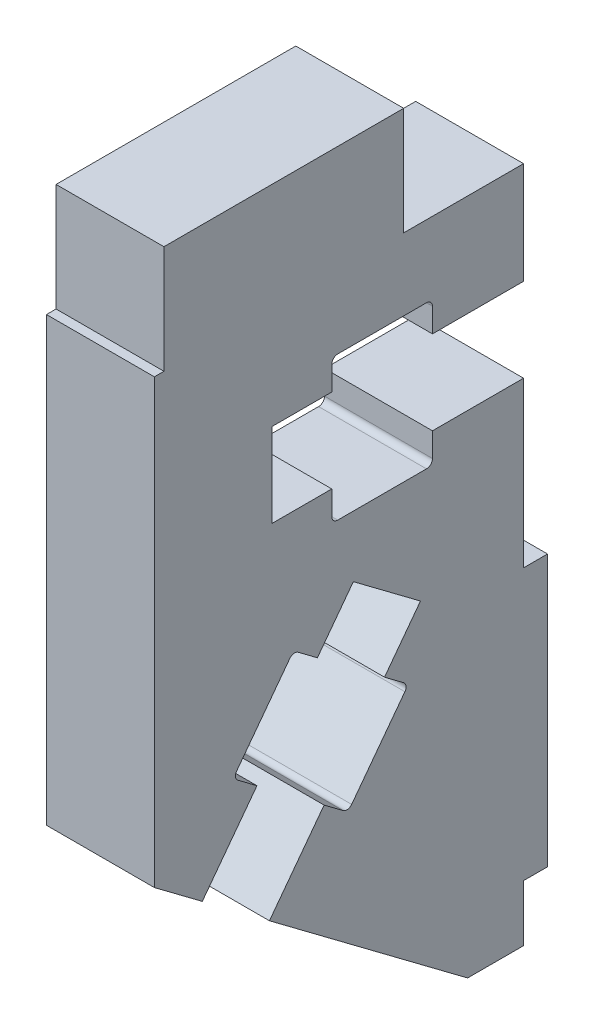
SolidWorks part; units mm, degrees
ref_plane "Front Plane" through (0, 0, 0) normal (0, 0, 1) x (1, 0, 0)
ref_plane "Top Plane" through (0, 0, 0) normal (0, 1, 0) x (1, 0, 0)
ref_plane "Right Plane" through (0, 0, 0) normal (1, 0, 0) x (0, 0, -1)
sketch "Sketch1" plane through (0, 0, 0) normal (1, 0, 0) x (0, 0, -1)
  line L0 (0, 0) -> (0, -30)
  line L1 (0, -30) -> (-40, 0)
  line L2 (-40, 0) -> (0, 0)
  dimension "D1" = 40
  dimension "D2" = 30
extrude "Boss-Extrude1" add sketch "Sketch1" along normal blind 4.5
sketch "Sketch2" plane through (4.5, 0, 0) normal (1, 0, 0) x (0, 0, -1)
  line L0 (0, -25.9) -> (1, -25.9)
  line L1 (0, -30) -> (0, 0) construction
  line L2 (1, -25.9) -> (1, -14.6)
  line L3 (1, -14.6) -> (0, -14.6)
  line L4 (0, -14.6) -> (0, -25.9)
  line L5 (1, -20.25) -> (0, -20.25) construction
  line L6 (0, -14.5) -> (4.5, -14.5) construction
  line L7 (0, -26) -> (4.5, -26) construction
  dimension "D2" = 1
  dimension "D3" = 0.1
  dimension "D1" = 0.1
extrude "Boss-Extrude2" add sketch "Sketch2" against normal through all
sketch "Sketch3" plane through (4.5, 0, 0) normal (1, 0, 0) x (0, 0, -1)
  line L0 (0, -6) -> (-10.5, -6) construction
  line L1 (0, -14.6) -> (0, 0) construction
  line L2 (-10.5, -7.75) -> (-10.5, -4.25) construction
  line L3 (-10.5, -4.25) -> (0, -4.25) construction
  line L4 (0, -4.25) -> (-3.8, -4.25)
  line L5 (-3.8, -4.25) -> (-3.8, -3.25)
  line L6 (-4.05, -3) -> (-7.75, -3)
  line L7 (-8, -3.25) -> (-8, -4.25)
  line L8 (-8, -4.25) -> (-10.5, -4.25)
  line L9 (-10.5, -4.25) -> (-10.5, -7.75)
  line L10 (0, -4.25) -> (0, -7.75)
  line L12 (-10.5, -7.75) -> (0, -7.75) construction
  line L13 (-8, -7.75) -> (-10.5, -7.75)
  line L14 (-8, -8.75) -> (-8, -7.75)
  line L15 (-4.05, -9) -> (-7.75, -9)
  line L16 (-3.8, -7.75) -> (-3.8, -8.75)
  line L17 (0, -7.75) -> (-3.8, -7.75)
  arc A0 (-3.8, -3.25) -> (-4.05, -3) centre (-4.05, -3.25) ccw
  arc A1 (-7.75, -3) -> (-8, -3.25) centre (-7.75, -3.25) ccw
  arc A2 (-7.75, -9) -> (-8, -8.75) centre (-7.75, -8.75) cw
  arc A3 (-3.8, -8.75) -> (-4.05, -9) centre (-4.05, -8.75) cw
  point P15 (-3.8, -3)
  point P18 (-8, -3)
  point P29 (-8, -9)
  point P30 (-3.8, -9)
  dimension "D7" = 0.25
  dimension "D1" = 10.5
  dimension "D2" = 1.75
  dimension "D3" = 4.2
  dimension "D4" = 3
  dimension "D5" = 8
  dimension "D6" = 6
extrude "Cut-Extrude1" cut sketch "Sketch3" against normal through all
sketch "Sketch4" plane through (4.5, 0, 0) normal (1, 0, 0) x (0, 0, -1)
  line L0 (-13.4, -19.95) -> (-7.1, -11.55) construction
  line L1 (-40, 0) -> (0, -30) construction
  line L2 (-7.1, -11.55) -> (-4.3, -13.65) construction
  line L3 (-5.7, -12.6) -> (-12, -21) construction
  line L4 (-10.6, -22.05) -> (-13.4, -19.95)
  line L5 (-13.4, -19.95) -> (-11.12, -16.91)
  line L6 (-11.12, -16.91) -> (-11.92, -16.31)
  line L7 (-11.97, -15.96) -> (-9.75, -13)
  line L8 (-9.4, -12.95) -> (-8.6, -13.55)
  line L9 (-8.6, -13.55) -> (-7.1, -11.55)
  line L10 (-7.1, -11.55) -> (-4.3, -13.65)
  line L11 (0, 0) -> (-40, 0) construction
  line L12 (-10.6, -22.05) -> (-4.3, -13.65) construction
  line L13 (-5.8, -15.65) -> (-4.3, -13.65)
  line L14 (-5, -16.25) -> (-5.8, -15.65)
  line L15 (-7.17, -19.56) -> (-4.95, -16.6)
  line L16 (-8.32, -19.01) -> (-7.52, -19.61)
  line L17 (-10.6, -22.05) -> (-8.32, -19.01)
  arc A0 (-11.92, -16.31) -> (-11.97, -15.96) centre (-11.77, -16.11) cw
  arc A1 (-9.75, -13) -> (-9.4, -12.95) centre (-9.55, -13.15) cw
  arc A2 (-4.95, -16.6) -> (-5, -16.25) centre (-5.15, -16.45) ccw
  arc A3 (-7.52, -19.61) -> (-7.17, -19.56) centre (-7.37, -19.41) ccw
  point P14 (-12.12, -16.16)
  point P17 (-9.6, -12.8)
  point P28 (-4.8, -16.4)
  point P29 (-7.32, -19.76)
  dimension "D7" = 0.25
  dimension "D1" = 10.5
  dimension "D2" = 1.75
  dimension "D3" = 4.2
  dimension "D4" = 3
  dimension "D5" = 8
  dimension "D6" = 21
extrude "Cut-Extrude2" cut sketch "Sketch4" against normal through all
sketch "Sketch5" plane through (4.5, 0, 0) normal (1, 0, 0) x (0, 0, -1)
  line L0 (-15.4, -18.45) -> (-15.4, 0)
  line L1 (-40, 0) -> (-13.4, -19.95) construction
  line L2 (0, 0) -> (-40, 0) construction
  line L3 (-15.4, 0) -> (-40, 0)
  line L4 (-40, 0) -> (-15.4, -18.45)
  dimension "D1" = 2
extrude "Cut-Extrude3" cut sketch "Sketch5" against normal through all
sketch "Sketch6" plane through (0, 0, 10.5) normal (0, 0, -1) x (-1, 0, 0)
  line L0 (-2.25, -4.25) -> (-2.25, -7.75) construction
  line L1 (0, -4.25) -> (-4.5, -4.25) construction
  line L2 (0, -7.75) -> (-4.5, -7.75) construction
  circle A0 centre (-2.25, -6) radius 1.5
  dimension "D1" = 3
sketch "Sketch7" plane through (0, -10.8, 8.1) normal (0, -0.8, 0.6) x (1, 0, 0)
  line L0 (2.25, -1.25) -> (2.25, -4.75) construction
  line L1 (0, -1.25) -> (4.5, -1.25) construction
  line L2 (0, -4.75) -> (4.5, -4.75) construction
  circle A0 centre (2.25, -3) radius 1.75
sketch "Sketch8" plane through (4.5, 0, 0) normal (1, 0, 0) x (0, 0, -1)
  line L0 (-10, 4.5) -> (-10, 0) construction
  line L1 (-15, 0) -> (-5, 0)
  line L2 (-15, 0) -> (-15, 4.5)
  line L3 (-15, 4.5) -> (-5, 4.5)
  line L4 (-5, 0) -> (-5, 4.5)
  line L5 (0, 0) -> (-15.4, 0) construction
  dimension "D2" = 4.5
  dimension "D3" = 10
extrude "Boss-Extrude3" add sketch "Sketch8" against normal through all
sketch "Sketch10" plane through (4.5, 0, 0) normal (1, 0, 0) x (0, 0, -1)
  line L0 (0, -28.25) -> (-2.3333, -28.25)
  line L1 (0, -30) -> (0, -25.9) construction
  line L2 (-10.6, -22.05) -> (0, -30) construction
  line L3 (-2.3333, -28.25) -> (0, -30)
  line L4 (0, -30) -> (0, -28.25)
  dimension "D1" = 0
extrude "Cut-Extrude4" cut sketch "Sketch10" against normal through all contours L0 L3 L4
equation "\"X-ROD-SPACING\"=45"
equation "\"Y-ROD-SPACING\"=75"
equation "\"Z-ROD-SPACING\"=17.5"
equation "\"Y-BED-OFFSET\"=2"
equation "\"Y-BED-ROD-INSET\"=3.5"
equation "\"Y-BED-SCREW-SPACING\"=209"
equation "\"Y-BED-SCREW-CUTOUT-SLOT-HEIGHT\"=2"
equation "\"T-SLOT-NUT-FILLET-RADIUS\"=0.25"
equation "\"T-SLOT-SCREW-SHAFT-RADIUS\"=1.75"
equation "\"T-SLOT-SCREW-SHAFT-CUTOUT-LENGTH\"=10.5"
equation "\"T-SLOT-NUT-DEPTH\"=4.2"
equation "\"T-SLOT-NUT-WIDTH\"=3"
equation "\"T-SLOT-NUT-END-DISTANCE\"=8"
equation "\"ACRYLIC-THICKNESS\"=10"
equation "\"ACRYLIC-THICKNESS2\"=4.5"
equation "\"ACRYLIC-TAB-CUTOUT-SIZE\"=\"ACRYLIC-THICKNESS\"+\"ACRYLIC-TAB-TOLERANCE\"*2"
equation "\"ACRYLIC-TAB-TOLERANCE\"=.1"
equation "\"ACRYLIC-TAB-WIDTH\"=\"ACRYLIC-THICKNESS\""
equation "\"ACRYLIC-M3-HOLE\"=3.1"
equation "\"SMOOTHROD-CAP-SCREW-DISTANCE\"=20"
equation "\"FRAME-WIDTH-INNER\"=370"
equation "\"NEMA17-HOLE-SPACING\"=31"
equation "\"NEMA17-CENTRAL-CUTOUT\"=22.5"
equation "\"Z-BRACKET-REACH\"=55"
equation "\"Z-ROD-INSET\"=16"
equation "\"TOP-BRACKET-SPACING\"=40"
equation "\"SMOOTHROD-X-LENGTH\"=350"
equation "\"SMOOTHROD-Y-LENGTH\"=350"
equation "\"SMOOTHROD-Z-LENGTH\"=350"
equation "\"SMOOTHROD-TIGHTENING-HEADROOM\"=.25"
equation "\"LEADSCREW-Z-LENGTH\"=300"
equation "\"SCREW-LENGTH-FRAME\"=\"ACRYLIC-THICKNESS\" + 10"
equation "\"SCREW-LENGTH-MOTOR\"=\"ACRYLIC-THICKNESS\" + 5"
equation "\"SCREW-LENGTH-EXTRUDER\"=28"
equation "\"SCREW-HEAD-RADIUS\"=6"
equation "\"PRINTED-M3-HOLE\"=3.5"
equation "\"PRINTED-X-SMOOTHROD-DIAMETER\"=8.2"
equation "\"PRINTED-X-SMOOTHROD-CUTOUT\"=10"
equation "\"PRINTED-X-BASE-HEIGHT\"=10"
equation "\"PRINTED-LM8UU-CUTOUT-SIZE\"=15.25"
equation "\"PRINTED-LM8UU-CUTOUT-LENGTH\"=24.5"
equation "\"PRINTED-X-IDLER-HEIGHT\"=16"
equation "\"PRINTED-M3-NUT-AF\"=6.25"
equation "\"PSU-MOUNTING-WIDTH\"=95"
equation "\"PSU-MOUNTING-HEIGHT\"=177"
equation "\"Y-BELT-TO-ROD-DISTANCE\"=20"
equation "\"SPOOL-HOLDER-ROD-SPACING\"=150"
equation "\"ACRYLIC-X-CARRIAGE-WIDTH\"=55"
equation "\"ACRYLIC-X-CARRIAGE-HEIGHT\"=75"
equation "\"ACRYLIC-X-CARRIAGE-LM8UU-CUTOUT-WIDTH\"=24.25"
equation "\"ACRYLIC-X-CARRIAGE-LM8UU-CUTOUT-HEIGHT\"=11.5"
equation "\"ACRYLIC-X-CARRIAGE-SCREW-SPACING-X\"=15"
equation "\"ACRYLIC-X-CARRIAGE-SCREW-SPACING-Y\"=33"
equation "\"ACRYLIC-X-CARRIAGE-CENTER-TAB-SPACING\"=14"
equation "\"ACRYLIC-X-CARRIAGE-EXTRUDER-OFFSET\"=26"
equation "\"ACRYLIC-X-CARRIAGE-EXTRUDER-ANGLE\"=90"
equation "\"ACRYLIC-X-CARRIAGE-EXTRUDER-SHELF-DEPTH\"=\"ACRYLIC-X-CARRIAGE-EXTRUDER-OFFSET\" + 28"
equation "\"ACRYLIC-X-CARRIAGE-EXTRUDER-BRACE-SPACING\"=23"
equation "\"ACRYLIC-X-CARRIAGE-EXTRUDER-BRACE-TAB-OFFSET\"=20"
equation "\"ACRYLIC-X-CARRIAGE-EXTRUDER-BRACE-HEIGHT\"=35"
equation "\"ACRYLIC-X-CARRIAGE-EXTRUDER-BRACE-SCREW-SPACING\"=22"
equation "\"ACRYLIC-X-CARRIAGE-DUAL-WIDTH-MULTIPLIER\"=1.65"
equation "\"ACRYLIC-X-CARRIAGE-DUAL-HOTEND-SPACING\"=42"
equation "\"ACRYLIC-X-CARRIAGE-DUAL-WIDTH\"=75"
equation "\"ACRYLIC-X-CARRIAGE-DUAL-FAN-OFFSET\"=52"
equation "\"ACRYLIC-X-CARRIAGE-DUAL-FAN-HEIGHT\"=20"
equation "\"ACRYLIC-X-CARRIAGE-DUAL-HOTEND-SEPARATION\"=36"
equation "\"ACRYLIC-X-CARRIAGE-DUAL-MOUNT-PLATE-DEPTH\"=75"
equation "\"ACRYLIC-X-CARRIAGE-DUAL-MOUNT-BRACE-WIDTH\"=33"
equation "\"ACRYLIC-X-CARRIAGE-DUAL-MOUNT-SCREW-WIDTH\"=40"
equation "\"BLOWER-FAN-WIDTH\"=15"
equation "\"D1@Boss-Extrude1\"=\"ACRYLIC-THICKNESS2\""
equation "\"D1@Sketch2\"=\"ACRYLIC-TAB-TOLERANCE\""
equation "\"D1@Sketch3\"=\"T-SLOT-SCREW-SHAFT-CUTOUT-LENGTH\""
equation "\"D2@Sketch3\"=\"T-SLOT-SCREW-SHAFT-RADIUS\""
equation "\"D3@Sketch3\"=\"T-SLOT-NUT-DEPTH\""
equation "\"D4@Sketch3\"=\"T-SLOT-NUT-WIDTH\""
equation "\"D5@Sketch3\"=\"T-SLOT-NUT-END-DISTANCE\""
equation "\"D7@Sketch3\"=\"T-SLOT-NUT-FILLET-RADIUS\""
equation "\"D1@Sketch4\"=\"T-SLOT-SCREW-SHAFT-CUTOUT-LENGTH\""
equation "\"D2@Sketch4\"=\"T-SLOT-SCREW-SHAFT-RADIUS\""
equation "\"D3@Sketch4\"=\"T-SLOT-NUT-DEPTH\""
equation "\"D4@Sketch4\"=\"T-SLOT-NUT-WIDTH\""
equation "\"D5@Sketch4\"=\"T-SLOT-NUT-END-DISTANCE\""
equation "\"D7@Sketch4\"=\"T-SLOT-NUT-FILLET-RADIUS\""
equation "\"D1@Sketch8\"=\"ACRYLIC-TAB-WIDTH\""
equation "\"D2@Sketch8\"=\"ACRYLIC-THICKNESS2\""
equation "\"D3@Sketch2\"=\"ACRYLIC-TAB-TOLERANCE\""
